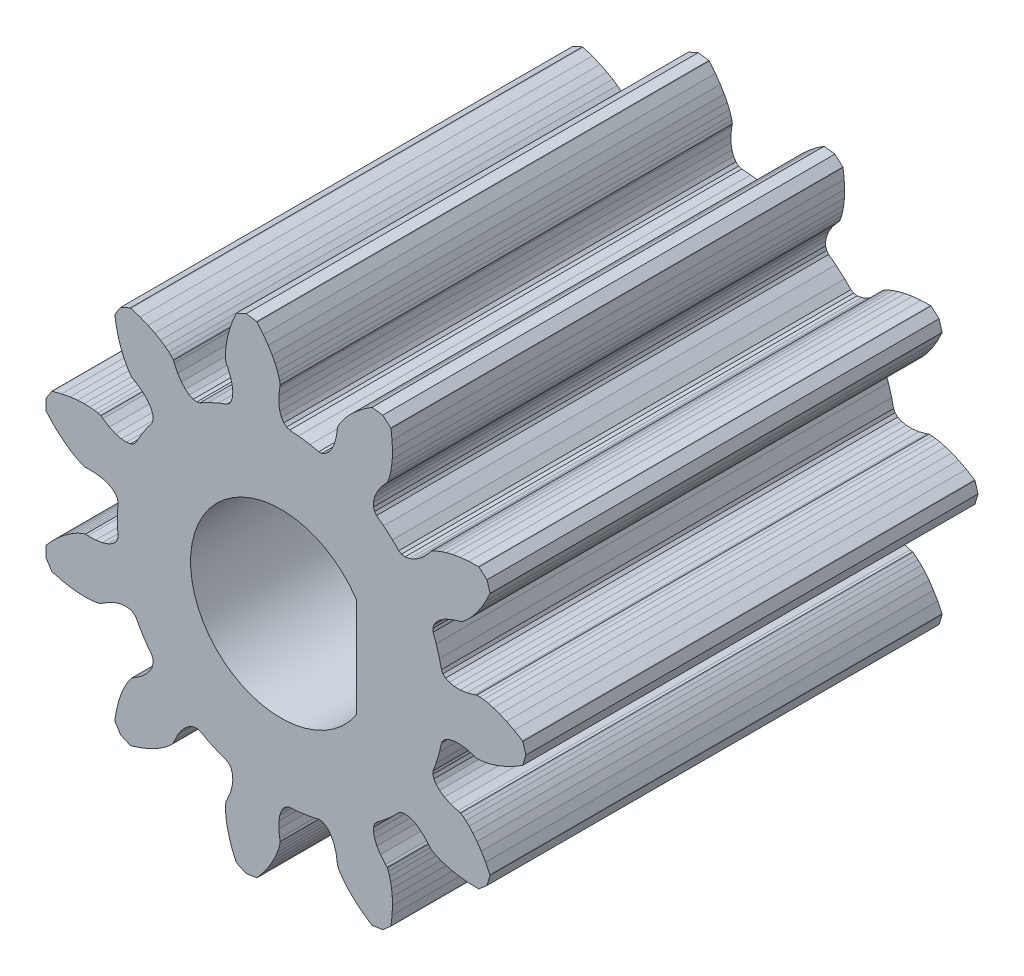
SolidWorks part; units mm, degrees
ref_plane "Front Plane" through (0, 0, 0) normal (0, 0, 1) x (1, 0, 0)
ref_plane "Top Plane" through (0, 0, 0) normal (0, 1, 0) x (1, 0, 0)
ref_plane "Right Plane" through (0, 0, 0) normal (1, 0, 0) x (0, 0, -1)
sketch "Model" plane through (0, 0, 0) normal (0, 0, 1) x (1, 0, 0)
  line L0 (6.5648, -4.627) -> (6.8352, -4.3927)
  line L1 (6.8352, -4.3927) -> (6.936, -4.0495)
  line L2 (6.936, -4.0495) -> (6.9285, -4.0309)
  line L3 (6.9285, -4.0309) -> (6.7886, -3.7457)
  line L4 (6.7886, -3.7457) -> (6.6455, -3.4999)
  line L5 (6.6455, -3.4999) -> (6.5039, -3.2924)
  line L6 (6.5039, -3.2924) -> (6.3685, -3.1214)
  line L7 (6.3685, -3.1214) -> (6.2436, -2.9851)
  line L8 (6.2436, -2.9851) -> (6.1334, -2.8808)
  line L9 (6.1334, -2.8808) -> (6.0417, -2.8056)
  line L10 (6.0417, -2.8056) -> (5.972, -2.7563)
  line L11 (5.972, -2.7563) -> (5.9521, -2.7443)
  line L12 (5.9521, -2.7443) -> (5.8732, -2.7294)
  line L13 (5.8732, -2.7294) -> (5.6285, -2.6518)
  line L14 (5.6285, -2.6518) -> (5.425, -2.5557)
  line L15 (5.425, -2.5557) -> (5.2639, -2.4466)
  line L16 (5.2639, -2.4466) -> (5.1458, -2.33)
  line L17 (5.1458, -2.33) -> (5.0708, -2.2115)
  line L18 (5.0708, -2.2115) -> (5.0384, -2.0966)
  line L19 (5.0384, -2.0966) -> (5.0475, -1.9908)
  line L20 (5.0475, -1.9908) -> (5.1507, -1.7143)
  line L21 (5.1507, -1.7143) -> (5.2598, -1.3425)
  line L22 (5.2598, -1.3425) -> (5.3226, -1.0541)
  line L23 (5.3226, -1.0541) -> (5.3721, -0.9602)
  line L24 (5.3721, -0.9602) -> (5.4615, -0.881)
  line L25 (5.4615, -0.881) -> (5.5886, -0.8219)
  line L26 (5.5886, -0.8219) -> (5.751, -0.7876)
  line L27 (5.751, -0.7876) -> (5.9455, -0.783)
  line L28 (5.9455, -0.783) -> (6.1687, -0.8121)
  line L29 (6.1687, -0.8121) -> (6.4165, -0.8792)
  line L30 (6.4165, -0.8792) -> (6.4909, -0.9093)
  line L31 (6.4909, -0.9093) -> (6.5142, -0.9099)
  line L32 (6.5142, -0.9099) -> (6.5995, -0.9062)
  line L33 (6.5995, -0.9062) -> (6.7172, -0.8925)
  line L34 (6.7172, -0.8925) -> (6.8663, -0.8644)
  line L35 (6.8663, -0.8644) -> (7.0451, -0.8172)
  line L36 (7.0451, -0.8172) -> (7.2514, -0.7466)
  line L37 (7.2514, -0.7466) -> (7.4828, -0.6485)
  line L38 (7.4828, -0.6485) -> (7.7361, -0.5191)
  line L39 (7.7361, -0.5191) -> (8.0079, -0.3548)
  line L40 (8.0079, -0.3548) -> (8.0242, -0.3432)
  line L41 (8.0242, -0.3432) -> (8.125, 0)
  line L42 (8.125, 0) -> (8.0242, 0.3432)
  line L43 (8.0242, 0.3432) -> (8.0079, 0.3548)
  line L44 (8.0079, 0.3548) -> (7.7361, 0.5191)
  line L45 (7.7361, 0.5191) -> (7.4828, 0.6485)
  line L46 (7.4828, 0.6485) -> (7.2514, 0.7466)
  line L47 (7.2514, 0.7466) -> (7.0451, 0.8172)
  line L48 (7.0451, 0.8172) -> (6.8663, 0.8644)
  line L49 (6.8663, 0.8644) -> (6.7172, 0.8925)
  line L50 (6.7172, 0.8925) -> (6.5995, 0.9062)
  line L51 (6.5995, 0.9062) -> (6.5142, 0.9099)
  line L52 (6.5142, 0.9099) -> (6.4909, 0.9093)
  line L53 (6.4909, 0.9093) -> (6.4165, 0.8792)
  line L54 (6.4165, 0.8792) -> (6.1687, 0.8121)
  line L55 (6.1687, 0.8121) -> (5.9455, 0.783)
  line L56 (5.9455, 0.783) -> (5.751, 0.7876)
  line L57 (5.751, 0.7876) -> (5.5886, 0.8219)
  line L58 (5.5886, 0.8219) -> (5.4615, 0.881)
  line L59 (5.4615, 0.881) -> (5.3721, 0.9602)
  line L60 (5.3721, 0.9602) -> (5.3226, 1.0541)
  line L61 (5.3226, 1.0541) -> (5.2598, 1.3425)
  line L62 (5.2598, 1.3425) -> (5.1507, 1.7143)
  line L63 (5.1507, 1.7143) -> (5.0475, 1.9908)
  line L64 (5.0475, 1.9908) -> (5.0384, 2.0966)
  line L65 (5.0384, 2.0966) -> (5.0708, 2.2115)
  line L66 (5.0708, 2.2115) -> (5.1458, 2.33)
  line L67 (5.1458, 2.33) -> (5.2639, 2.4466)
  line L68 (5.2639, 2.4466) -> (5.425, 2.5557)
  line L69 (5.425, 2.5557) -> (5.6285, 2.6518)
  line L70 (5.6285, 2.6518) -> (5.8732, 2.7294)
  line L71 (5.8732, 2.7294) -> (5.9521, 2.7443)
  line L72 (5.9521, 2.7443) -> (5.972, 2.7563)
  line L73 (5.972, 2.7563) -> (6.0417, 2.8056)
  line L74 (6.0417, 2.8056) -> (6.1334, 2.8808)
  line L75 (6.1334, 2.8808) -> (6.2436, 2.9851)
  line L76 (6.2436, 2.9851) -> (6.3685, 3.1214)
  line L77 (6.3685, 3.1214) -> (6.5039, 3.2924)
  line L78 (6.5039, 3.2924) -> (6.6455, 3.4999)
  line L79 (6.6455, 3.4999) -> (6.7886, 3.7457)
  line L80 (6.7886, 3.7457) -> (6.9285, 4.0309)
  line L81 (6.9285, 4.0309) -> (6.936, 4.0495)
  line L82 (6.936, 4.0495) -> (6.8352, 4.3927)
  line L83 (6.8352, 4.3927) -> (6.5648, 4.627)
  line L84 (6.5648, 4.627) -> (6.5448, 4.6278)
  line L85 (6.5448, 4.6278) -> (6.2273, 4.6191)
  line L86 (6.2273, 4.6191) -> (5.9443, 4.5911)
  line L87 (5.9443, 4.5911) -> (5.6967, 4.5485)
  line L88 (5.6967, 4.5485) -> (5.4849, 4.4963)
  line L89 (5.4849, 4.4963) -> (5.309, 4.4394)
  line L90 (5.309, 4.4394) -> (5.1683, 4.3824)
  line L91 (5.1683, 4.3824) -> (5.0619, 4.3303)
  line L92 (5.0619, 4.3303) -> (4.9881, 4.2873)
  line L93 (4.9881, 4.2873) -> (4.9689, 4.2742)
  line L94 (4.9689, 4.2742) -> (4.9226, 4.2086)
  line L95 (4.9226, 4.2086) -> (4.7504, 4.0183)
  line L96 (4.7504, 4.0183) -> (4.5784, 3.8731)
  line L97 (4.5784, 3.8731) -> (4.4122, 3.7718)
  line L98 (4.4122, 3.7718) -> (4.2571, 3.7128)
  line L99 (4.2571, 3.7128) -> (4.1182, 3.6939)
  line L100 (4.1182, 3.6939) -> (4.0002, 3.7121)
  line L101 (4.0002, 3.7121) -> (3.9077, 3.7644)
  line L102 (3.9077, 3.7644) -> (3.699, 3.9731)
  line L103 (3.699, 3.9731) -> (3.4062, 4.2268)
  line L104 (3.4062, 4.2268) -> (3.1699, 4.4037)
  line L105 (3.1699, 4.4037) -> (3.105, 4.4878)
  line L106 (3.105, 4.4878) -> (3.0702, 4.6019)
  line L107 (3.0702, 4.6019) -> (3.0692, 4.7422)
  line L108 (3.0692, 4.7422) -> (3.1055, 4.9041)
  line L109 (3.1055, 4.9041) -> (3.1821, 5.083)
  line L110 (3.1821, 5.083) -> (3.3013, 5.2739)
  line L111 (3.3013, 5.2739) -> (3.4652, 5.4714)
  line L112 (3.4652, 5.4714) -> (3.5236, 5.5266)
  line L113 (3.5236, 5.5266) -> (3.5338, 5.5475)
  line L114 (3.5338, 5.5475) -> (3.5658, 5.6266)
  line L115 (3.5658, 5.6266) -> (3.6023, 5.7394)
  line L116 (3.6023, 5.7394) -> (3.6386, 5.8867)
  line L117 (3.6386, 5.8867) -> (3.6699, 6.069)
  line L118 (3.6699, 6.069) -> (3.6915, 6.286)
  line L119 (3.6915, 6.286) -> (3.6984, 6.5372)
  line L120 (3.6984, 6.5372) -> (3.6859, 6.8213)
  line L121 (3.6859, 6.8213) -> (3.6493, 7.1368)
  line L122 (3.6493, 7.1368) -> (3.6456, 7.1565)
  line L123 (3.6456, 7.1565) -> (3.3752, 7.3908)
  line L124 (3.3752, 7.3908) -> (3.0212, 7.4417)
  line L125 (3.0212, 7.4417) -> (3.0039, 7.4316)
  line L126 (3.0039, 7.4316) -> (2.7415, 7.2526)
  line L127 (2.7415, 7.2526) -> (2.5185, 7.076)
  line L128 (2.5185, 7.076) -> (2.3332, 6.9063)
  line L129 (2.3332, 6.9063) -> (2.1833, 6.7479)
  line L130 (2.1833, 6.7479) -> (2.0661, 6.6049)
  line L131 (2.0661, 6.6049) -> (1.9786, 6.481)
  line L132 (1.9786, 6.481) -> (1.9172, 6.3795)
  line L133 (1.9172, 6.3795) -> (1.8784, 6.3035)
  line L134 (1.8784, 6.3035) -> (1.8693, 6.2821)
  line L135 (1.8693, 6.2821) -> (1.8658, 6.2019)
  line L136 (1.8658, 6.2019) -> (1.8238, 5.9486)
  line L137 (1.8238, 5.9486) -> (1.7577, 5.7335)
  line L138 (1.7577, 5.7335) -> (1.6726, 5.5585)
  line L139 (1.6726, 5.5585) -> (1.574, 5.425)
  line L140 (1.574, 5.425) -> (1.4674, 5.3339)
  line L141 (1.4674, 5.3339) -> (1.3583, 5.2855)
  line L142 (1.3583, 5.2855) -> (1.2522, 5.2795)
  line L143 (1.2522, 5.2795) -> (0.9638, 5.3422)
  line L144 (0.9638, 5.3422) -> (0.5803, 5.3974)
  line L145 (0.5803, 5.3974) -> (0.2859, 5.4184)
  line L146 (0.2859, 5.4184) -> (0.1858, 5.4541)
  line L147 (0.1858, 5.4541) -> (0.0948, 5.5313)
  line L148 (0.0948, 5.5313) -> (0.0182, 5.6487)
  line L149 (0.0182, 5.6487) -> (-0.0388, 5.8045)
  line L150 (-0.0388, 5.8045) -> (-0.0711, 5.9964)
  line L151 (-0.0711, 5.9964) -> (-0.074, 6.2215)
  line L152 (-0.074, 6.2215) -> (-0.0429, 6.4763)
  line L153 (-0.0429, 6.4763) -> (-0.0237, 6.5543)
  line L154 (-0.0237, 6.5543) -> (-0.0264, 6.5773)
  line L155 (-0.0264, 6.5773) -> (-0.0422, 6.6612)
  line L156 (-0.0422, 6.6612) -> (-0.0725, 6.7759)
  line L157 (-0.0725, 6.7759) -> (-0.1216, 6.9194)
  line L158 (-0.1216, 6.9194) -> (-0.1938, 7.0897)
  line L159 (-0.1938, 7.0897) -> (-0.293, 7.2839)
  line L160 (-0.293, 7.2839) -> (-0.423, 7.4989)
  line L161 (-0.423, 7.4989) -> (-0.5871, 7.7312)
  line L162 (-0.5871, 7.7312) -> (-0.7885, 7.9768)
  line L163 (-0.7885, 7.9768) -> (-0.8022, 7.9914)
  line L164 (-0.8022, 7.9914) -> (-1.1563, 8.0423)
  line L165 (-1.1563, 8.0423) -> (-1.4817, 7.8937)
  line L166 (-1.4817, 7.8937) -> (-1.4908, 7.8759)
  line L167 (-1.4908, 7.8759) -> (-1.6148, 7.5834)
  line L168 (-1.6148, 7.5834) -> (-1.7068, 7.3143)
  line L169 (-1.7068, 7.3143) -> (-1.771, 7.0714)
  line L170 (-1.771, 7.0714) -> (-1.8115, 6.8571)
  line L171 (-1.8115, 6.8571) -> (-1.8327, 6.6734)
  line L172 (-1.8327, 6.6734) -> (-1.8394, 6.5218)
  line L173 (-1.8394, 6.5218) -> (-1.8362, 6.4033)
  line L174 (-1.8362, 6.4033) -> (-1.8277, 6.3184)
  line L175 (-1.8277, 6.3184) -> (-1.8238, 6.2955)
  line L176 (-1.8238, 6.2955) -> (-1.7834, 6.2261)
  line L177 (-1.7834, 6.2261) -> (-1.6818, 5.9903)
  line L178 (-1.6818, 5.9903) -> (-1.6211, 5.7736)
  line L179 (-1.6211, 5.7736) -> (-1.5981, 5.5804)
  line L180 (-1.5981, 5.5804) -> (-1.6089, 5.4148)
  line L181 (-1.6089, 5.4148) -> (-1.6493, 5.2805)
  line L182 (-1.6493, 5.2805) -> (-1.7149, 5.1808)
  line L183 (-1.7149, 5.1808) -> (-1.8009, 5.1184)
  line L184 (-1.8009, 5.1184) -> (-2.0774, 5.0152)
  line L185 (-2.0774, 5.0152) -> (-2.4299, 4.8543)
  line L186 (-2.4299, 4.8543) -> (-2.6889, 4.7128)
  line L187 (-2.6889, 4.7128) -> (-2.7923, 4.6887)
  line L188 (-2.7923, 4.6887) -> (-2.9107, 4.7044)
  line L189 (-2.9107, 4.7044) -> (-3.0386, 4.7618)
  line L190 (-3.0386, 4.7618) -> (-3.1708, 4.8621)
  line L191 (-3.1708, 4.8621) -> (-3.3018, 5.0061)
  line L192 (-3.3018, 5.0061) -> (-3.4259, 5.1938)
  line L193 (-3.4259, 5.1938) -> (-3.5375, 5.425)
  line L194 (-3.5375, 5.425) -> (-3.5635, 5.501)
  line L195 (-3.5635, 5.501) -> (-3.5782, 5.5189)
  line L196 (-3.5782, 5.5189) -> (-3.6369, 5.581)
  line L197 (-3.6369, 5.581) -> (-3.7243, 5.661)
  line L198 (-3.7243, 5.661) -> (-3.8432, 5.7552)
  line L199 (-3.8432, 5.7552) -> (-3.996, 5.8594)
  line L200 (-3.996, 5.8594) -> (-4.1844, 5.9692)
  line L201 (-4.1844, 5.9692) -> (-4.4101, 6.0798)
  line L202 (-4.4101, 6.0798) -> (-4.6737, 6.1865)
  line L203 (-4.6737, 6.1865) -> (-4.9759, 6.2843)
  line L204 (-4.9759, 6.2843) -> (-4.9953, 6.2891)
  line L205 (-4.9953, 6.2891) -> (-5.3207, 6.1405)
  line L206 (-5.3207, 6.1405) -> (-5.5141, 5.8395)
  line L207 (-5.5141, 5.8395) -> (-5.5122, 5.8196)
  line L208 (-5.5122, 5.8196) -> (-5.4584, 5.5066)
  line L209 (-5.4584, 5.5066) -> (-5.3903, 5.2304)
  line L210 (-5.3903, 5.2304) -> (-5.3129, 4.9914)
  line L211 (-5.3129, 4.9914) -> (-5.2311, 4.7892)
  line L212 (-5.2311, 4.7892) -> (-5.1497, 4.6232)
  line L213 (-5.1497, 4.6232) -> (-5.0734, 4.492)
  line L214 (-5.0734, 4.492) -> (-5.0066, 4.3941)
  line L215 (-5.0066, 4.3941) -> (-4.9535, 4.3272)
  line L216 (-4.9535, 4.3272) -> (-4.9379, 4.3101)
  line L217 (-4.9379, 4.3101) -> (-4.8663, 4.2735)
  line L218 (-4.8663, 4.2735) -> (-4.6534, 4.1301)
  line L219 (-4.6534, 4.1301) -> (-4.4852, 3.9806)
  line L220 (-4.4852, 3.9806) -> (-4.3614, 3.8305)
  line L221 (-4.3614, 3.8305) -> (-4.2809, 3.6854)
  line L222 (-4.2809, 3.6854) -> (-4.2423, 3.5505)
  line L223 (-4.2423, 3.5505) -> (-4.2436, 3.4312)
  line L224 (-4.2436, 3.4312) -> (-4.2822, 3.3322)
  line L225 (-4.2822, 3.3322) -> (-4.459, 3.096)
  line L226 (-4.459, 3.096) -> (-4.6686, 2.77)
  line L227 (-4.6686, 2.77) -> (-4.81, 2.511)
  line L228 (-4.81, 2.511) -> (-4.884, 2.4348)
  line L229 (-4.884, 2.4348) -> (-4.992, 2.384)
  line L230 (-4.992, 2.384) -> (-5.1307, 2.3631)
  line L231 (-5.1307, 2.3631) -> (-5.2961, 2.376)
  line L232 (-5.2961, 2.376) -> (-5.4841, 2.4263)
  line L233 (-5.4841, 2.4263) -> (-5.69, 2.5172)
  line L234 (-5.69, 2.5172) -> (-5.9089, 2.6513)
  line L235 (-5.9089, 2.6513) -> (-5.9718, 2.7012)
  line L236 (-5.9718, 2.7012) -> (-5.9939, 2.7083)
  line L237 (-5.9939, 2.7083) -> (-6.0768, 2.7288)
  line L238 (-6.0768, 2.7288) -> (-6.1937, 2.7488)
  line L239 (-6.1937, 2.7488) -> (-6.3447, 2.7638)
  line L240 (-6.3447, 2.7638) -> (-6.5295, 2.7689)
  line L241 (-6.5295, 2.7689) -> (-6.7474, 2.7593)
  line L242 (-6.7474, 2.7593) -> (-6.997, 2.7304)
  line L243 (-6.997, 2.7304) -> (-7.2764, 2.6776)
  line L244 (-7.2764, 2.6776) -> (-7.5835, 2.5965)
  line L245 (-7.5835, 2.5965) -> (-7.6025, 2.59)
  line L246 (-7.6025, 2.59) -> (-7.7959, 2.2891)
  line L247 (-7.7959, 2.2891) -> (-7.7959, 1.9314)
  line L248 (-7.7959, 1.9314) -> (-7.7834, 1.9157)
  line L249 (-7.7834, 1.9157) -> (-7.5689, 1.6814)
  line L250 (-7.5689, 1.6814) -> (-7.3624, 1.4859)
  line L251 (-7.3624, 1.4859) -> (-7.168, 1.3266)
  line L252 (-7.168, 1.3266) -> (-6.9899, 1.2008)
  line L253 (-6.9899, 1.2008) -> (-6.8317, 1.1051)
  line L254 (-6.8317, 1.1051) -> (-6.6966, 1.0361)
  line L255 (-6.6966, 1.0361) -> (-6.5874, 0.9898)
  line L256 (-6.5874, 0.9898) -> (-6.5066, 0.9622)
  line L257 (-6.5066, 0.9622) -> (-6.4842, 0.9563)
  line L258 (-6.4842, 0.9563) -> (-6.4043, 0.9642)
  line L259 (-6.4043, 0.9642) -> (-6.1476, 0.9587)
  line L260 (-6.1476, 0.9587) -> (-5.9253, 0.9238)
  line L261 (-5.9253, 0.9238) -> (-5.7399, 0.8645)
  line L262 (-5.7399, 0.8645) -> (-5.5938, 0.7859)
  line L263 (-5.5938, 0.7859) -> (-5.4884, 0.6933)
  line L264 (-5.4884, 0.6933) -> (-5.425, 0.5922)
  line L265 (-5.425, 0.5922) -> (-5.4039, 0.4881)
  line L266 (-5.4039, 0.4881) -> (-5.425, 0.1938)
  line L267 (-5.425, 0.1938) -> (-5.425, -0.1938)
  line L268 (-5.425, -0.1938) -> (-5.4039, -0.4881)
  line L269 (-5.4039, -0.4881) -> (-5.425, -0.5922)
  line L270 (-5.425, -0.5922) -> (-5.4884, -0.6933)
  line L271 (-5.4884, -0.6933) -> (-5.5938, -0.7859)
  line L272 (-5.5938, -0.7859) -> (-5.7399, -0.8645)
  line L273 (-5.7399, -0.8645) -> (-5.9253, -0.9238)
  line L274 (-5.9253, -0.9238) -> (-6.1476, -0.9587)
  line L275 (-6.1476, -0.9587) -> (-6.4043, -0.9642)
  line L276 (-6.4043, -0.9642) -> (-6.4842, -0.9563)
  line L277 (-6.4842, -0.9563) -> (-6.5066, -0.9622)
  line L278 (-6.5066, -0.9622) -> (-6.5874, -0.9898)
  line L279 (-6.5874, -0.9898) -> (-6.6966, -1.0361)
  line L280 (-6.6966, -1.0361) -> (-6.8317, -1.1051)
  line L281 (-6.8317, -1.1051) -> (-6.9899, -1.2008)
  line L282 (-6.9899, -1.2008) -> (-7.168, -1.3266)
  line L283 (-7.168, -1.3266) -> (-7.3624, -1.4859)
  line L284 (-7.3624, -1.4859) -> (-7.5689, -1.6814)
  line L285 (-7.5689, -1.6814) -> (-7.7834, -1.9157)
  line L286 (-7.7834, -1.9157) -> (-7.7959, -1.9314)
  line L287 (-7.7959, -1.9314) -> (-7.7959, -2.2891)
  line L288 (-7.7959, -2.2891) -> (-7.6025, -2.59)
  line L289 (-7.6025, -2.59) -> (-7.5835, -2.5965)
  line L290 (-7.5835, -2.5965) -> (-7.2764, -2.6776)
  line L291 (-7.2764, -2.6776) -> (-6.997, -2.7304)
  line L292 (-6.997, -2.7304) -> (-6.7474, -2.7593)
  line L293 (-6.7474, -2.7593) -> (-6.5295, -2.7689)
  line L294 (-6.5295, -2.7689) -> (-6.3447, -2.7638)
  line L295 (-6.3447, -2.7638) -> (-6.1937, -2.7488)
  line L296 (-6.1937, -2.7488) -> (-6.0768, -2.7288)
  line L297 (-6.0768, -2.7288) -> (-5.9939, -2.7083)
  line L298 (-5.9939, -2.7083) -> (-5.9718, -2.7012)
  line L299 (-5.9718, -2.7012) -> (-5.9089, -2.6513)
  line L300 (-5.9089, -2.6513) -> (-5.69, -2.5172)
  line L301 (-5.69, -2.5172) -> (-5.4841, -2.4263)
  line L302 (-5.4841, -2.4263) -> (-5.2961, -2.376)
  line L303 (-5.2961, -2.376) -> (-5.1307, -2.3631)
  line L304 (-5.1307, -2.3631) -> (-4.992, -2.384)
  line L305 (-4.992, -2.384) -> (-4.884, -2.4348)
  line L306 (-4.884, -2.4348) -> (-4.81, -2.511)
  line L307 (-4.81, -2.511) -> (-4.6686, -2.77)
  line L308 (-4.6686, -2.77) -> (-4.459, -3.096)
  line L309 (-4.459, -3.096) -> (-4.2822, -3.3322)
  line L310 (-4.2822, -3.3322) -> (-4.2436, -3.4312)
  line L311 (-4.2436, -3.4312) -> (-4.2423, -3.5505)
  line L312 (-4.2423, -3.5505) -> (-4.2809, -3.6854)
  line L313 (-4.2809, -3.6854) -> (-4.3614, -3.8305)
  line L314 (-4.3614, -3.8305) -> (-4.4852, -3.9806)
  line L315 (-4.4852, -3.9806) -> (-4.6534, -4.1301)
  line L316 (-4.6534, -4.1301) -> (-4.8663, -4.2735)
  line L317 (-4.8663, -4.2735) -> (-4.9379, -4.3101)
  line L318 (-4.9379, -4.3101) -> (-4.9535, -4.3272)
  line L319 (-4.9535, -4.3272) -> (-5.0066, -4.3941)
  line L320 (-5.0066, -4.3941) -> (-5.0734, -4.492)
  line L321 (-5.0734, -4.492) -> (-5.1497, -4.6232)
  line L322 (-5.1497, -4.6232) -> (-5.2311, -4.7892)
  line L323 (-5.2311, -4.7892) -> (-5.3129, -4.9914)
  line L324 (-5.3129, -4.9914) -> (-5.3903, -5.2304)
  line L325 (-5.3903, -5.2304) -> (-5.4584, -5.5066)
  line L326 (-5.4584, -5.5066) -> (-5.5122, -5.8196)
  line L327 (-5.5122, -5.8196) -> (-5.5141, -5.8395)
  line L328 (-5.5141, -5.8395) -> (-5.3207, -6.1405)
  line L329 (-5.3207, -6.1405) -> (-4.9953, -6.2891)
  line L330 (-4.9953, -6.2891) -> (-4.9759, -6.2843)
  line L331 (-4.9759, -6.2843) -> (-4.6737, -6.1865)
  line L332 (-4.6737, -6.1865) -> (-4.4101, -6.0798)
  line L333 (-4.4101, -6.0798) -> (-4.1844, -5.9692)
  line L334 (-4.1844, -5.9692) -> (-3.996, -5.8594)
  line L335 (-3.996, -5.8594) -> (-3.8432, -5.7552)
  line L336 (-3.8432, -5.7552) -> (-3.7243, -5.661)
  line L337 (-3.7243, -5.661) -> (-3.6369, -5.581)
  line L338 (-3.6369, -5.581) -> (-3.5782, -5.5189)
  line L339 (-3.5782, -5.5189) -> (-3.5635, -5.501)
  line L340 (-3.5635, -5.501) -> (-3.5375, -5.425)
  line L341 (-3.5375, -5.425) -> (-3.4259, -5.1938)
  line L342 (-3.4259, -5.1938) -> (-3.3018, -5.0061)
  line L343 (-3.3018, -5.0061) -> (-3.1708, -4.8621)
  line L344 (-3.1708, -4.8621) -> (-3.0386, -4.7618)
  line L345 (-3.0386, -4.7618) -> (-2.9107, -4.7044)
  line L346 (-2.9107, -4.7044) -> (-2.7923, -4.6887)
  line L347 (-2.7923, -4.6887) -> (-2.6889, -4.7128)
  line L348 (-2.6889, -4.7128) -> (-2.4299, -4.8543)
  line L349 (-2.4299, -4.8543) -> (-2.0774, -5.0152)
  line L350 (-2.0774, -5.0152) -> (-1.8009, -5.1184)
  line L351 (-1.8009, -5.1184) -> (-1.7149, -5.1808)
  line L352 (-1.7149, -5.1808) -> (-1.6493, -5.2805)
  line L353 (-1.6493, -5.2805) -> (-1.6089, -5.4148)
  line L354 (-1.6089, -5.4148) -> (-1.5981, -5.5804)
  line L355 (-1.5981, -5.5804) -> (-1.6211, -5.7736)
  line L356 (-1.6211, -5.7736) -> (-1.6818, -5.9903)
  line L357 (-1.6818, -5.9903) -> (-1.7834, -6.2261)
  line L358 (-1.7834, -6.2261) -> (-1.8238, -6.2955)
  line L359 (-1.8238, -6.2955) -> (-1.8277, -6.3184)
  line L360 (-1.8277, -6.3184) -> (-1.8362, -6.4033)
  line L361 (-1.8362, -6.4033) -> (-1.8394, -6.5218)
  line L362 (-1.8394, -6.5218) -> (-1.8327, -6.6734)
  line L363 (-1.8327, -6.6734) -> (-1.8115, -6.8571)
  line L364 (-1.8115, -6.8571) -> (-1.771, -7.0714)
  line L365 (-1.771, -7.0714) -> (-1.7068, -7.3143)
  line L366 (-1.7068, -7.3143) -> (-1.6148, -7.5834)
  line L367 (-1.6148, -7.5834) -> (-1.4908, -7.8759)
  line L368 (-1.4908, -7.8759) -> (-1.4817, -7.8937)
  line L369 (-1.4817, -7.8937) -> (-1.1563, -8.0423)
  line L370 (-1.1563, -8.0423) -> (-0.8022, -7.9914)
  line L371 (-0.8022, -7.9914) -> (-0.7885, -7.9768)
  line L372 (-0.7885, -7.9768) -> (-0.5871, -7.7312)
  line L373 (-0.5871, -7.7312) -> (-0.423, -7.4989)
  line L374 (-0.423, -7.4989) -> (-0.293, -7.2839)
  line L375 (-0.293, -7.2839) -> (-0.1938, -7.0897)
  line L376 (-0.1938, -7.0897) -> (-0.1216, -6.9194)
  line L377 (-0.1216, -6.9194) -> (-0.0725, -6.7759)
  line L378 (-0.0725, -6.7759) -> (-0.0422, -6.6612)
  line L379 (-0.0422, -6.6612) -> (-0.0264, -6.5773)
  line L380 (-0.0264, -6.5773) -> (-0.0237, -6.5543)
  line L381 (-0.0237, -6.5543) -> (-0.0429, -6.4763)
  line L382 (-0.0429, -6.4763) -> (-0.074, -6.2215)
  line L383 (-0.074, -6.2215) -> (-0.0711, -5.9964)
  line L384 (-0.0711, -5.9964) -> (-0.0388, -5.8045)
  line L385 (-0.0388, -5.8045) -> (0.0182, -5.6487)
  line L386 (0.0182, -5.6487) -> (0.0948, -5.5313)
  line L387 (0.0948, -5.5313) -> (0.1858, -5.4541)
  line L388 (0.1858, -5.4541) -> (0.2859, -5.4184)
  line L389 (0.2859, -5.4184) -> (0.5803, -5.3974)
  line L390 (0.5803, -5.3974) -> (0.9638, -5.3422)
  line L391 (0.9638, -5.3422) -> (1.2522, -5.2795)
  line L392 (1.2522, -5.2795) -> (1.3583, -5.2855)
  line L393 (1.3583, -5.2855) -> (1.4674, -5.3339)
  line L394 (1.4674, -5.3339) -> (1.574, -5.425)
  line L395 (1.574, -5.425) -> (1.6726, -5.5585)
  line L396 (1.6726, -5.5585) -> (1.7577, -5.7335)
  line L397 (1.7577, -5.7335) -> (1.8238, -5.9486)
  line L398 (1.8238, -5.9486) -> (1.8658, -6.2019)
  line L399 (1.8658, -6.2019) -> (1.8693, -6.2821)
  line L400 (1.8693, -6.2821) -> (1.8784, -6.3035)
  line L401 (1.8784, -6.3035) -> (1.9172, -6.3795)
  line L402 (1.9172, -6.3795) -> (1.9786, -6.481)
  line L403 (1.9786, -6.481) -> (2.0661, -6.6049)
  line L404 (2.0661, -6.6049) -> (2.1833, -6.7479)
  line L405 (2.1833, -6.7479) -> (2.3332, -6.9063)
  line L406 (2.3332, -6.9063) -> (2.5185, -7.076)
  line L407 (2.5185, -7.076) -> (2.7415, -7.2526)
  line L408 (2.7415, -7.2526) -> (3.0039, -7.4316)
  line L409 (3.0039, -7.4316) -> (3.0212, -7.4417)
  line L410 (3.0212, -7.4417) -> (3.3752, -7.3908)
  line L411 (3.3752, -7.3908) -> (3.6456, -7.1565)
  line L412 (3.6456, -7.1565) -> (3.6493, -7.1368)
  line L413 (3.6493, -7.1368) -> (3.6859, -6.8213)
  line L414 (3.6859, -6.8213) -> (3.6984, -6.5372)
  line L415 (3.6984, -6.5372) -> (3.6915, -6.286)
  line L416 (3.6915, -6.286) -> (3.6699, -6.069)
  line L417 (3.6699, -6.069) -> (3.6386, -5.8867)
  line L418 (3.6386, -5.8867) -> (3.6023, -5.7394)
  line L419 (3.6023, -5.7394) -> (3.5658, -5.6266)
  line L420 (3.5658, -5.6266) -> (3.5338, -5.5475)
  line L421 (3.5338, -5.5475) -> (3.5236, -5.5266)
  line L422 (3.5236, -5.5266) -> (3.4652, -5.4714)
  line L423 (3.4652, -5.4714) -> (3.3013, -5.2739)
  line L424 (3.3013, -5.2739) -> (3.1821, -5.083)
  line L425 (3.1821, -5.083) -> (3.1055, -4.9041)
  line L426 (3.1055, -4.9041) -> (3.0692, -4.7422)
  line L427 (3.0692, -4.7422) -> (3.0702, -4.6019)
  line L428 (3.0702, -4.6019) -> (3.105, -4.4878)
  line L429 (3.105, -4.4878) -> (3.1699, -4.4037)
  line L430 (3.1699, -4.4037) -> (3.4062, -4.2268)
  line L431 (3.4062, -4.2268) -> (3.699, -3.9731)
  line L432 (3.699, -3.9731) -> (3.9077, -3.7644)
  line L433 (3.9077, -3.7644) -> (4.0002, -3.7121)
  line L434 (4.0002, -3.7121) -> (4.1182, -3.6939)
  line L435 (4.1182, -3.6939) -> (4.2571, -3.7128)
  line L436 (4.2571, -3.7128) -> (4.4122, -3.7718)
  line L437 (4.4122, -3.7718) -> (4.5784, -3.8731)
  line L438 (4.5784, -3.8731) -> (4.7504, -4.0183)
  line L439 (4.7504, -4.0183) -> (4.9226, -4.2086)
  line L440 (4.9226, -4.2086) -> (4.9689, -4.2742)
  line L441 (4.9689, -4.2742) -> (4.9881, -4.2873)
  line L442 (4.9881, -4.2873) -> (5.0619, -4.3303)
  line L443 (5.0619, -4.3303) -> (5.1683, -4.3824)
  line L444 (5.1683, -4.3824) -> (5.309, -4.4394)
  line L445 (5.309, -4.4394) -> (5.4849, -4.4963)
  line L446 (5.4849, -4.4963) -> (5.6967, -4.5485)
  line L447 (5.6967, -4.5485) -> (5.9443, -4.5911)
  line L448 (5.9443, -4.5911) -> (6.2273, -4.6191)
  line L449 (6.2273, -4.6191) -> (6.5448, -4.6278)
  line L450 (6.5448, -4.6278) -> (6.5648, -4.627)
  line L451 (2.5, 1.6583) -> (2.5, -1.6583)
  circle A0 centre (0, 0) radius 3
  dimension "D1" = 6
  dimension "D2" = 2.5
extrude "Boss-Extrude1" add sketch "Model" along normal blind 15 contours L451 A0 | L449 L450 L0 L1 L2 L3 L4 L5 L6 L7 L8 L9 L10 L11 L12 L13 L14 L15 L16 L17 L18 L19 L20 L21 L22 L23 L24 L25 L26 L27 L28 L29 L30 L31 L32 L33 L34 L35 L36 L37 L38 L39 L40 L41 L42 L43 L44 L45 L46 L47 L48 region at (6.5449, -4.4013, 0) region at (2.7015, 0, 0)
